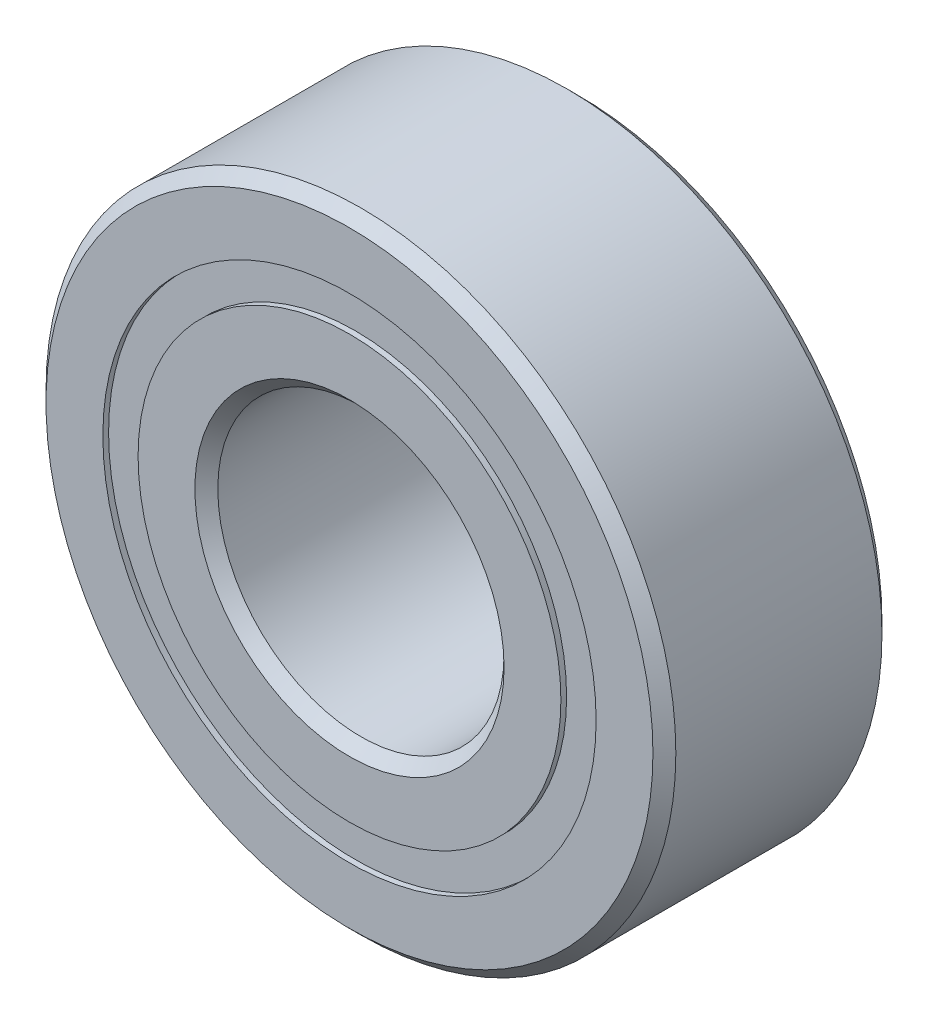
SolidWorks part; units mm, degrees
ref_plane "Front Plane" through (0, 0, 0) normal (0, 0, 1) x (1, 0, 0)
ref_plane "Top Plane" through (0, 0, 0) normal (0, 1, 0) x (1, 0, 0)
ref_plane "Right Plane" through (0, 0, 0) normal (1, 0, 0) x (0, 0, -1)
sketch "Sketch1" plane through (0, 0, 0) normal (1, 0, 0) x (0, 0, -1)
  line L0 (-2, 0) -> (2, 0) construction
  line L1 (0, 5.5) -> (0, -5.5) construction
  line L2 (1.8, 5.5) -> (-1.8, 5.5)
  line L3 (-1.8, 5.5) -> (-2, 5.3)
  line L4 (-2, 5.3) -> (-2, 4.3077)
  line L5 (-2, 4.3077) -> (-0.8889, 4.3077)
  line L6 (2, 4.3077) -> (0.8889, 4.3077)
  line L7 (2, 5.3) -> (2, 4.3077)
  line L8 (1.8, 5.5) -> (2, 5.3)
  line L9 (0, 5.5) -> (0, 4) construction
  line L10 (0, 4) -> (0, 2.5) construction
  arc A0 (-0.8889, 4.3077) -> (0.8889, 4.3077) centre (0, 4) cw
  point P14 (0, 2.5)
  dimension "D3" = 1.7778
  dimension "D1" = 45
  dimension "Width" = 4
  dimension "OD" = 11
  dimension "D2" = 0.2
  dimension "Shaft Dia" = 5
  dimension "D4" = 0.3077
revolve "Revolve1" add sketch "Sketch1" angle 360 about L0
sketch "Sketch3" plane through (0, 0, 0) normal (1, 0, 0) x (0, 0, -1)
  line L0 (-2, 3.6923) -> (-0.8889, 3.6923)
  line L1 (0, 5.5) -> (0, -5.5) construction
  line L2 (-2, 5.3) -> (-2, 4.3077) construction
  line L3 (-2, 3.6923) -> (-2, 2.7)
  line L4 (-1.8, 5.5) -> (-2, 5.3) construction
  line L5 (-2, 2.7) -> (-1.8, 2.5)
  line L6 (-1.8, 2.5) -> (1.8, 2.5)
  line L7 (1.8, 5.5) -> (1.8, -5.5) construction
  line L8 (1.8, 2.5) -> (2, 2.7)
  line L9 (2, -5.3) -> (2, 5.3) construction
  line L10 (2, 2.7) -> (2, 3.6923)
  line L11 (2, 3.6923) -> (0.8889, 3.6923)
  line L13 (1.8, 5.5) -> (2, 5.3) construction
  arc A0 (0.8889, 4.3077) -> (-0.8889, 4.3077) centre (0, 4) ccw construction
  arc A1 (0.8889, 3.6923) -> (-0.8889, 3.6923) centre (0, 4) cw
revolve "Revolve3" add sketch "Sketch3" angle 360 about L0
sketch "Sketch4" plane through (0, 0, 0) normal (1, 0, 0) x (0, 0, -1)
  line L0 (-0.9406, 4) -> (0.9406, 4)
  arc A2 (-0.9406, 4) -> (0.9406, 4) centre (0, 4) cw
  arc A3 (0.8889, 4.3077) -> (-0.8889, 4.3077) centre (0, 4) ccw construction
revolve "Revolve4" add sketch "Sketch4" angle 360 about L0
ref_axis "Axis1" through (0, 0, -2) along (0, 0, 1)
pattern_circular "CirPattern1" count 12 every 30 about axis through (0, 0, -2) along (0, 0, 1) of bodies 104
sketch "Sketch5" plane through (0, 0, 0) normal (1, 0, 0) x (0, 0, -1)
  line L0 (-2, 4.3077) -> (-0.8889, 4.3077) construction
  line L1 (-1.9, 4.3077) -> (-0.9406, 4.3077)
  line L2 (-1.9, 4.3077) -> (-1.9, 3.6923)
  line L3 (-1.9, 3.6923) -> (-0.9406, 3.6923)
  line L4 (-0.9406, 4.3077) -> (-0.9406, 3.6923)
  line L5 (-2, 3.6923) -> (-0.8889, 3.6923) construction
  line L6 (2, 4.3077) -> (0.8889, 4.3077) construction
  line L7 (1.9, 4.3077) -> (0.9406, 4.3077)
  line L8 (1.9, 4.3077) -> (1.9, 3.6923)
  line L9 (1.9, 3.6923) -> (0.9406, 3.6923)
  line L10 (0.9406, 4.3077) -> (0.9406, 3.6923)
  line L11 (2, 3.6923) -> (0.8889, 3.6923) construction
  line L12 (-1.8, 5.5) -> (-2, 5.3) construction
  point P18 (-1.9, 5.4)
revolve "Revolve5" add sketch "Sketch5" angle 360 about L0
sketch "Sketch6" plane through (0, 0, 0) normal (1, 0, 0) x (0, 0, -1)
  line L0 (2, 0) -> (-2, 0) construction
  line L1 (2, 4.3077) -> (0.9, 4.3077)
  line L2 (2, 4.3077) -> (2, 9.5)
  line L3 (2, 9.5) -> (0.9, 9.5)
  line L4 (0.9, 4.3077) -> (0.9, 9.5)
  dimension "Th" = 1.1
  dimension "Flange OD" = 19
revolve "Revolve6" [suppressed] add sketch "Sketch6" angle 360 about L0
equation "\"D2@Sketch1\" = \"Width@Sketch1\"*.05"
equation "\"D3@Sketch1\" = \"Width@Sketch1\"/2.25"
equation "\"D4@Sketch1\" = (((\"OD@Sketch1\"-\"Width@Sketch1\")/2)/3.25)/3.5"
equation "\"D2@CirPattern1\" = 360/\"Balls@CirPattern1\""
